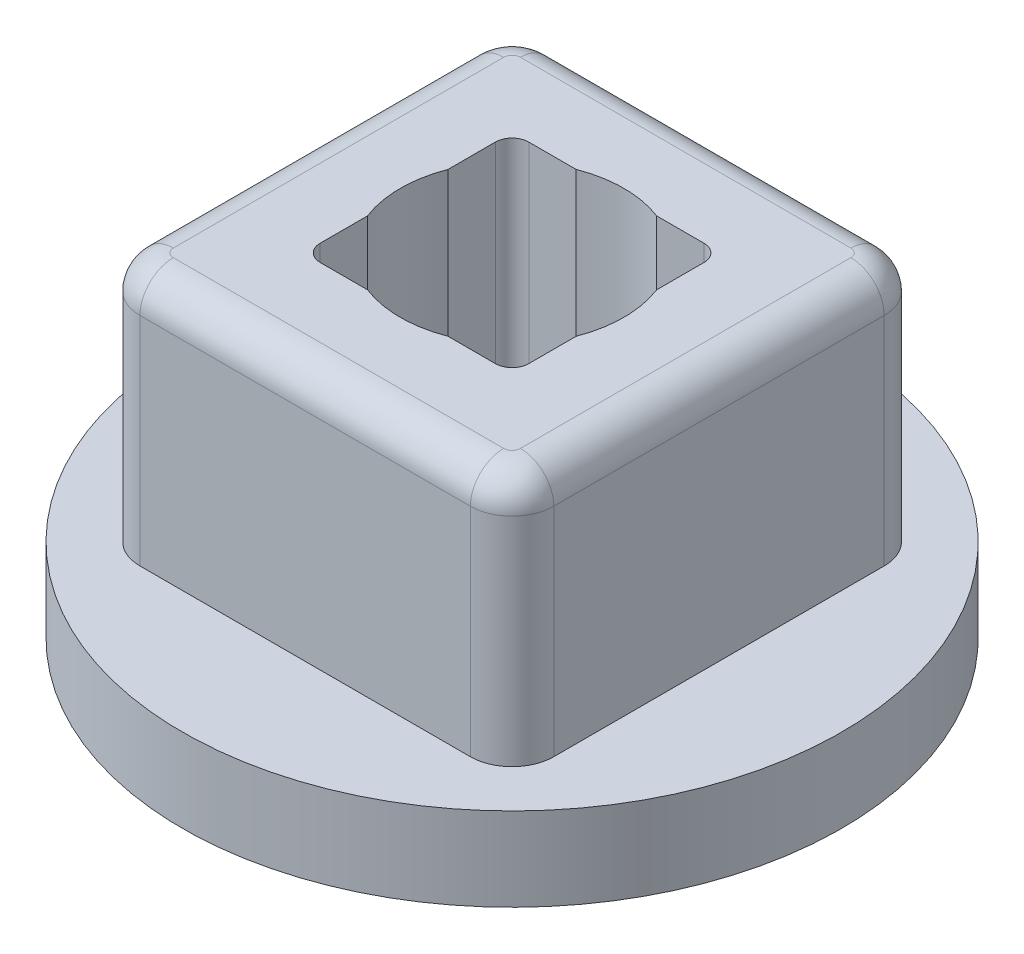
SolidWorks part; units mm, degrees
material "Custom Plastic"
ref_plane "Front Plane" through (0, 0, 0) normal (0, 0, 1) x (1, 0, 0)
ref_plane "Top Plane" through (0, 0, 0) normal (0, 1, 0) x (1, 0, 0)
ref_plane "Right Plane" through (0, 0, 0) normal (1, 0, 0) x (0, 0, -1)
sketch "Sketch1" plane through (0, 0, 0) normal (0, 0, 1) x (1, 0, 0)
  line L0 (5.0165, 1.27) -> (0, 1.27)
  line L1 (0, 1.27) -> (0, 0)
  line L2 (0, 0) -> (5.0165, 0)
  line L3 (5.0165, 0) -> (5.0165, 1.27)
  line L4 (0, 1.27) -> (0, 0) construction
revolve "Revolve1" add sketch "Sketch1" angle 360 about L4 reverse direction yes
sketch "Sketch2" plane through (0, 1.27, 0) normal (0, 1, 0) x (-1, 0, 0)
  line L0 (-3.1496, 3.1496) -> (3.1496, 3.1496)
  line L1 (3.1496, 3.1496) -> (3.1496, -3.1496)
  line L2 (3.1496, -3.1496) -> (-3.1496, -3.1496)
  line L3 (-3.1496, -3.1496) -> (-3.1496, 3.1496)
extrude "Boss-Extrude1" add sketch "Sketch2" along normal blind 3.81
sketch "Sketch3" plane through (0, 0, 0) normal (0, -1, 0) x (1, 0, 0)
  line L0 (-1.5875, -1.5875) -> (1.5875, -1.5875)
  line L1 (1.5875, -1.5875) -> (1.5875, 1.5875)
  line L2 (1.5875, 1.5875) -> (-1.5875, 1.5875)
  line L3 (-1.5875, 1.5875) -> (-1.5875, -1.5875)
extrude "Cut-Extrude1" cut sketch "Sketch3" against normal through all
fillet "Fillet1" radius 0.635 4 edges at (-3.1496, 3.175, 3.1496) (3.1496, 3.175, 3.1496) (-3.1496, 3.175, -3.1496) (3.1496, 3.175, -3.1496) tangent propagation no
fillet "Fillet2" radius 0.254 4 edges at (-1.5875, 2.54, 1.5875) (-1.5875, 2.54, -1.5875) (1.5875, 2.54, -1.5875) (1.5875, 2.54, 1.5875) tangent propagation no
fillet "Fillet3" radius 0.508 8 edges at (-3.1496, 5.08, 0) (-2.9636, 5.08, 2.9636) (-2.9636, 5.08, -2.9636) (0, 5.08, 3.1496) (0, 5.08, -3.1496) (2.9636, 5.08, 2.9636) (2.9636, 5.08, -2.9636) (3.1496, 5.08, 0) tangent propagation no
sketch "Sketch4" plane through (0, 5.08, 0) normal (0, 1, 0) x (1, 0, 0)
  circle A0 centre (0, 0) radius 1.7018
extrude "Cut-Extrude2" cut sketch "Sketch4" against normal blind 51.054
